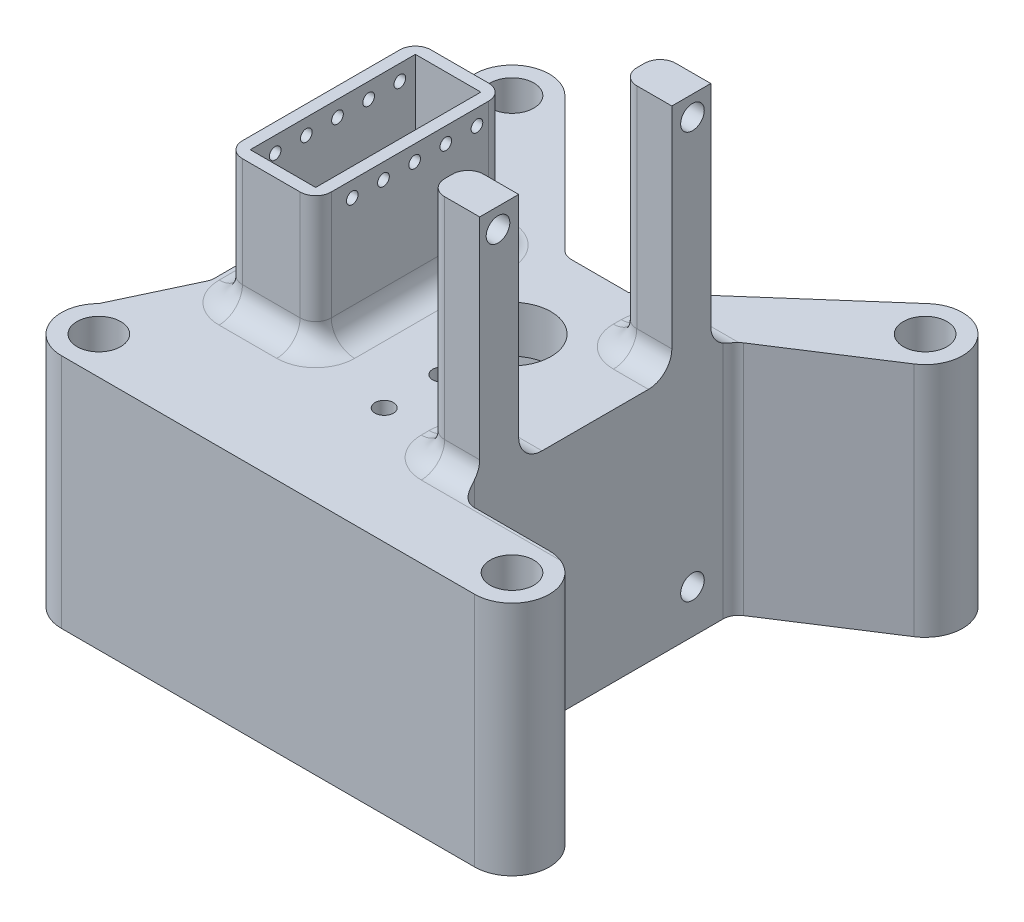
SolidWorks part; units mm, degrees
ref_plane "Front Plane" through (0, 0, 0) normal (0, 0, 1) x (1, 0, 0)
ref_plane "Top Plane" through (0, 0, 0) normal (0, 1, 0) x (1, 0, 0)
ref_plane "Right Plane" through (0, 0, 0) normal (1, 0, 0) x (0, 0, -1)
sketch "Sketch3" plane through (0, 0, 0) normal (0, 1, 0) x (1, 0, 0)
  line L0 (-33.676, -39.772) -> (33.676, -39.772)
  line L1 (-33.676, -33.676) -> (33.676, -33.676) construction
  line L2 (-33.676, -33.676) -> (-33.676, 33.676) construction
  line L3 (-33.676, 33.676) -> (33.676, 33.676) construction
  line L4 (33.676, -33.676) -> (33.676, 33.676) construction
  line L5 (-33.676, -33.676) -> (33.676, 33.676) construction
  line L6 (-33.676, 33.676) -> (33.676, -33.676) construction
  line L7 (10.033, -30.099) -> (-10.033, -30.099)
  line L8 (10.033, -30.099) -> (10.033, 10.033)
  line L9 (10.033, 10.033) -> (3.556, 10.033)
  line L10 (-10.033, -30.099) -> (-10.033, 10.033)
  line L11 (10.033, -30.099) -> (-10.033, 10.033) construction
  line L12 (10.033, 10.033) -> (-10.033, -30.099) construction
  line L13 (33.676, -27.58) -> (18.923, -27.58)
  line L14 (-3.556, 15.367) -> (3.556, 15.367) construction
  line L15 (-3.556, 15.367) -> (-3.556, 10.033)
  line L16 (0, 10.033) -> (3.556, 10.033) construction
  line L17 (3.556, 15.367) -> (3.556, 10.033)
  line L18 (-3.556, 15.367) -> (3.556, 10.033) construction
  line L19 (-3.556, 10.033) -> (3.556, 15.367) construction
  line L20 (-25.781, 10.033) -> (-15.113, 10.033) construction
  line L21 (-25.781, 10.033) -> (-25.781, -16.891) construction
  line L22 (-25.781, -16.891) -> (-15.113, -16.891) construction
  line L23 (-15.113, 10.033) -> (-15.113, -16.891) construction
  line L24 (-25.781, 10.033) -> (-15.113, -16.891) construction
  line L25 (-25.781, -16.891) -> (-15.113, 10.033) construction
  line L26 (18.923, -27.58) -> (18.923, 16.87)
  line L27 (36.9874, 28.5578) -> (18.923, 16.87)
  line L28 (29.6563, 38.259) -> (3.556, 15.367)
  line L31 (0, 10.033) -> (-3.556, 10.033) construction
  line L32 (-29.3669, 37.9879) -> (-6.731, 15.367)
  line L33 (-6.731, 15.367) -> (-3.556, 15.367)
  line L34 (-3.556, 10.033) -> (-10.033, 10.033)
  line L35 (-3.556, 10.033) -> (0, 10.033) construction
  line L36 (3.556, 10.033) -> (0, 10.033) construction
  line L37 (-32.131, -16.891) -> (-32.131, 10.033)
  line L38 (34.003, -24.1637) -> (18.923, -24.1637) construction
  line L39 (34.003, -24.1637) -> (34.003, 13.4537) construction
  line L40 (34.003, 13.4537) -> (18.923, 13.4537) construction
  line L41 (18.923, -24.1637) -> (18.923, 13.4537) construction
  line L42 (34.003, -24.1637) -> (18.923, 13.4537) construction
  line L43 (34.003, 13.4537) -> (18.923, -24.1637) construction
  line L44 (-32.131, 10.033) -> (-39.4519, 31.7268)
  line L45 (-32.131, -16.891) -> (-37.9865, -29.3654)
  circle A0 centre (-33.676, 33.676) radius 3.556
  circle A1 centre (33.676, 33.676) radius 3.556
  circle A2 centre (33.676, -33.676) radius 3.556
  circle A3 centre (-33.676, -33.676) radius 3.556
  circle A4 centre (0, 0) radius 6.35 construction
  circle A5 centre (0, 0) radius 10.033 construction
  circle A6 centre (0, 0) radius 63.373 construction
  arc A7 (33.676, -39.772) -> (33.676, -27.58) centre (33.676, -33.676) ccw
  arc A8 (-39.772, -33.676) -> (-33.676, -39.772) centre (-33.676, -33.676) ccw
  arc A9 (-29.3669, 37.9879) -> (-39.772, 33.676) centre (-33.676, 33.676) ccw
  arc A10 (36.9874, 28.5578) -> (29.6563, 38.259) centre (33.676, 33.676) ccw
  arc A11 (27.58, 33.676) -> (29.3654, 29.3654) centre (33.676, 33.676) ccw construction
  arc A12 (29.6563, 38.259) -> (27.58, 33.676) centre (33.676, 33.676) ccw construction
  arc A13 (29.3654, 29.3654) -> (33.676, 27.58) centre (33.676, 33.676) ccw construction
  arc A14 (33.676, 27.58) -> (36.9874, 28.5578) centre (33.676, 33.676) ccw construction
  arc A15 (-27.58, 33.676) -> (-29.3669, 37.9879) centre (-33.676, 33.676) ccw construction
  arc A16 (-29.3654, 29.3654) -> (-27.58, 33.676) centre (-33.676, 33.676) ccw construction
  arc A17 (-33.676, 27.58) -> (-29.3654, 29.3654) centre (-33.676, 33.676) ccw construction
  arc A18 (-39.772, 33.676) -> (-39.4519, 31.7268) centre (-33.676, 33.676) ccw
  arc A19 (-37.9865, -29.3654) -> (-39.772, -33.676) centre (-33.676, -33.676) ccw
  arc A20 (-29.3654, -29.3654) -> (-33.676, -27.58) centre (-33.676, -33.676) ccw construction
  arc A21 (-27.58, -33.676) -> (-29.3654, -29.3654) centre (-33.676, -33.676) ccw construction
  arc A22 (-33.676, -39.772) -> (-27.58, -33.676) centre (-33.676, -33.676) ccw construction
  arc A23 (33.676, -27.58) -> (29.3654, -29.3654) centre (33.676, -33.676) ccw construction
  arc A24 (29.3654, -29.3654) -> (27.58, -33.676) centre (33.676, -33.676) ccw construction
  arc A25 (27.58, -33.676) -> (33.676, -39.772) centre (33.676, -33.676) ccw construction
  arc A26 (-39.4519, 31.7268) -> (-33.676, 27.58) centre (-33.676, 33.676) ccw construction
  arc A27 (-33.676, -27.58) -> (-37.9865, -29.3654) centre (-33.676, -33.676) ccw construction
  point P0 (0, 0)
  point P10 (0, -10.033)
  point P25 (0, 12.7)
  point P30 (3.556, 12.7)
  point P32 (-20.447, -3.429)
  point P53 (18.923, -5.355)
  point P55 (26.463, -5.355)
  point P64 (-32.131, -3.429)
  dimension "D2" = 7.112
  dimension "D5" = 12.7
  dimension "D6" = 126.746
  dimension "D1" = 95.25
  dimension "D3" = 40.132
  dimension "D4" = 20.066
  dimension "D7" = 2.54
  dimension "D8" = 5.334
  dimension "D9" = 7.112
  dimension "D10" = 10.668
  dimension "D11" = 26.924
  dimension "D12" = 5.08
  dimension "D13" = 8.89
  dimension "D14" = 171.65
  dimension "D15" = 352.506
  dimension "D16" = 44.45
  dimension "D17" = 37.6174
  dimension "D18" = 3.175
  dimension "D19" = 30.16
  dimension "D21" = 6.35
  dimension "D20" = 67.3519
extrude "Boss-Extrude1" add sketch "Sketch3" along normal blind 21.463
sketch "Sketch4" plane through (0, 21.463, 0) normal (0, 1, 0) x (1, 0, 0)
  line L0 (-3.556, 15.367) -> (3.556, 15.367) construction
  line L1 (-3.556, 10.033) -> (3.556, 10.033) construction
  line L2 (3.556, 15.367) -> (-3.556, 15.367)
  line L3 (-3.556, 10.033) -> (3.556, 10.033)
  line L16 (-10.033, 10.033) -> (-3.556, 10.033)
  line L17 (-3.556, 10.033) -> (-3.556, 15.367)
  line L18 (-3.556, 15.367) -> (-6.731, 15.367)
  line L19 (-6.731, 15.367) -> (-29.3669, 37.9879)
  line L20 (-39.4519, 31.7268) -> (-32.131, 10.033)
  line L21 (-33.676, -39.772) -> (33.676, -39.772)
  line L22 (33.676, -27.58) -> (18.923, -27.58)
  line L23 (18.923, -27.58) -> (18.923, 16.87)
  line L24 (18.923, 16.87) -> (36.9874, 28.5578)
  line L25 (29.6563, 38.259) -> (3.556, 15.367)
  line L27 (3.556, 15.367) -> (3.556, 10.033)
  line L28 (3.556, 10.033) -> (10.033, 10.033)
  line L29 (10.033, 10.033) -> (10.033, -30.099)
  line L30 (10.033, -30.099) -> (-10.033, -30.099)
  line L31 (-10.033, -30.099) -> (-10.033, 10.033)
  line L32 (-10.033, 10.033) -> (-3.556, 10.033)
  line L33 (-3.556, 10.033) -> (-3.556, 15.367) construction
  line L34 (-3.556, 15.367) -> (-6.731, 15.367)
  line L35 (-6.731, 15.367) -> (-29.3669, 37.9879)
  line L37 (-33.676, -39.772) -> (33.676, -39.772)
  line L38 (33.676, -27.58) -> (18.923, -27.58)
  line L39 (18.923, -27.58) -> (18.923, 16.87)
  line L40 (18.923, 16.87) -> (36.9874, 28.5578)
  line L41 (29.6563, 38.259) -> (3.556, 15.367)
  line L43 (3.556, 15.367) -> (3.556, 10.033) construction
  line L44 (3.556, 10.033) -> (10.033, 10.033)
  line L45 (10.033, 10.033) -> (10.033, -30.099)
  line L46 (10.033, -30.099) -> (-10.033, -30.099)
  line L47 (-10.033, -30.099) -> (-10.033, 10.033)
  line L52 (-39.4519, 31.7268) -> (-32.131, 10.033)
  line L53 (-32.131, 10.033) -> (-32.131, -16.891)
  line L54 (-32.131, 10.033) -> (-32.131, -16.891)
  line L55 (-32.131, -16.891) -> (-37.9865, -29.3654)
  line L56 (-32.131, -16.891) -> (-37.9865, -29.3654)
  circle A3 centre (33.676, -33.676) radius 3.556 construction
  arc A4 (-29.3669, 37.9879) -> (-39.4519, 31.7268) centre (-33.676, 33.676) ccw
  arc A5 (-37.9865, -29.3654) -> (-33.676, -39.772) centre (-33.676, -33.676) ccw
  arc A6 (33.676, -39.772) -> (33.676, -27.58) centre (33.676, -33.676) ccw
  arc A7 (36.9874, 28.5578) -> (29.6563, 38.259) centre (33.676, 33.676) ccw
  arc A8 (-29.3669, 37.9879) -> (-39.4519, 31.7268) centre (-33.676, 33.676) ccw
  arc A9 (-37.9865, -29.3654) -> (-33.676, -39.772) centre (-33.676, -33.676) ccw
  arc A10 (33.676, -39.772) -> (33.676, -27.58) centre (33.676, -33.676) ccw
  arc A11 (36.9874, 28.5578) -> (29.6563, 38.259) centre (33.676, 33.676) ccw
  circle A12 centre (33.676, -33.676) radius 3.556
  circle A13 centre (33.676, 33.676) radius 3.556 construction
  circle A14 centre (33.676, 33.676) radius 3.556
  circle A15 centre (-33.676, 33.676) radius 3.556 construction
  circle A16 centre (-33.676, 33.676) radius 3.556
  circle A17 centre (-33.676, -33.676) radius 3.556 construction
  circle A18 centre (-33.676, -33.676) radius 3.556
  dimension "D1" = 0
extrude "Boss-Extrude2" add sketch "Sketch4" along normal blind 7.366
sketch "Sketch5" plane through (0, 28.829, 0) normal (0, 1, 0) x (1, 0, 0)
  line L8 (3.556, 15.367) -> (-6.731, 15.367)
  line L9 (-6.731, 15.367) -> (-29.3669, 37.9879)
  line L10 (-39.4519, 31.7268) -> (-32.131, 10.033)
  line L11 (-33.676, -39.772) -> (33.676, -39.772)
  line L12 (33.676, -27.58) -> (18.923, -27.58)
  line L13 (18.923, -27.58) -> (18.923, 16.87)
  line L14 (18.923, 16.87) -> (36.9874, 28.5578)
  line L15 (29.6563, 38.259) -> (3.556, 15.367)
  line L16 (3.556, 15.367) -> (-6.731, 15.367)
  line L17 (-6.731, 15.367) -> (-29.3669, 37.9879)
  line L19 (-33.676, -39.772) -> (33.676, -39.772)
  line L20 (33.676, -27.58) -> (18.923, -27.58)
  line L21 (18.923, -27.58) -> (18.923, 16.87)
  line L22 (18.923, 16.87) -> (36.9874, 28.5578)
  line L23 (29.6563, 38.259) -> (3.556, 15.367)
  line L26 (-39.4519, 31.7268) -> (-32.131, 10.033)
  line L27 (-32.131, 10.033) -> (-32.131, -16.891)
  line L28 (-32.131, 10.033) -> (-32.131, -16.891)
  line L29 (-32.131, -16.891) -> (-37.9865, -29.3654)
  line L30 (-32.131, -16.891) -> (-37.9865, -29.3654)
  circle A0 centre (0, 0) radius 6.35 construction
  circle A1 centre (33.676, 33.676) radius 3.556
  circle A2 centre (33.676, 33.676) radius 3.556
  circle A3 centre (-33.676, 33.676) radius 3.556
  circle A4 centre (-33.676, 33.676) radius 3.556
  circle A5 centre (-33.676, -33.676) radius 3.556
  circle A6 centre (-33.676, -33.676) radius 3.556
  circle A7 centre (33.676, -33.676) radius 3.556
  circle A8 centre (33.676, -33.676) radius 3.556
  circle A9 centre (0, 0) radius 6.35
  arc A12 (-29.3669, 37.9879) -> (-39.4519, 31.7268) centre (-33.676, 33.676) ccw
  arc A13 (-37.9865, -29.3654) -> (-33.676, -39.772) centre (-33.676, -33.676) ccw
  arc A14 (33.676, -39.772) -> (33.676, -27.58) centre (33.676, -33.676) ccw
  arc A15 (36.9874, 28.5578) -> (29.6563, 38.259) centre (33.676, 33.676) ccw
  arc A16 (-29.3669, 37.9879) -> (-39.4519, 31.7268) centre (-33.676, 33.676) ccw
  arc A17 (-37.9865, -29.3654) -> (-33.676, -39.772) centre (-33.676, -33.676) ccw
  arc A18 (33.676, -39.772) -> (33.676, -27.58) centre (33.676, -33.676) ccw
  arc A19 (36.9874, 28.5578) -> (29.6563, 38.259) centre (33.676, 33.676) ccw
  dimension "D1" = 0
  dimension "D2" = 0
  dimension "D3" = 0
  dimension "D4" = 0
  dimension "D5" = 0
extrude "Boss-Extrude3" add sketch "Sketch5" along normal blind 7.62
sketch "Sketch6" plane through (0, 36.449, 0) normal (0, 1, 0) x (1, 0, 0)
  line L0 (-25.781, 10.033) -> (-25.781, -16.891) construction
  line L1 (-25.781, -16.891) -> (-15.113, -16.891) construction
  line L2 (-15.113, 10.033) -> (-15.113, -16.891) construction
  line L3 (-25.781, 10.033) -> (-15.113, 10.033) construction
  line L4 (-25.781, 10.033) -> (-25.781, -16.891) construction
  line L5 (-25.781, -16.891) -> (-15.113, -16.891) construction
  line L6 (-15.113, 10.033) -> (-15.113, -16.891) construction
  line L7 (-25.781, 10.033) -> (-15.113, 10.033) construction
  line L9 (-13.208, 11.938) -> (-27.686, 11.938)
  line L10 (-13.208, 11.938) -> (-13.208, -18.796)
  line L11 (-13.208, -18.796) -> (-27.686, -18.796)
  line L12 (-27.686, 11.938) -> (-27.686, -18.796)
  line L13 (-13.208, 11.938) -> (-27.686, -18.796) construction
  line L14 (-13.208, -18.796) -> (-27.686, 11.938) construction
  point P4 (-20.447, -3.429)
  point P11 (-20.447, -16.891)
  dimension "D1" = 1.905
  dimension "D2" = 1.905
extrude "Boss-Extrude4" add sketch "Sketch6" along normal blind 21.59
sketch "Sketch7" plane through (0, 58.039, 0) normal (0, 1, 0) x (1, 0, 0)
  line L0 (-25.781, 10.033) -> (-25.781, -16.891) construction
  line L1 (-25.781, -16.891) -> (-15.113, -16.891) construction
  line L2 (-15.113, 10.033) -> (-15.113, -16.891) construction
  line L3 (-25.781, 10.033) -> (-15.113, 10.033) construction
  line L4 (-25.781, 10.033) -> (-25.781, -16.891)
  line L5 (-25.781, -16.891) -> (-15.113, -16.891)
  line L6 (-15.113, 10.033) -> (-15.113, -16.891)
  line L7 (-25.781, 10.033) -> (-15.113, 10.033)
extrude "Cut-Extrude1" cut sketch "Sketch7" against normal blind 50.8
sketch "Sketch8" plane through (-27.686, 0, 0) normal (-1, 0, 0) x (0, 0, 1)
  line L0 (16.891, 7.239) -> (16.891, 58.039) construction
  line L1 (-10.033, 7.239) -> (-10.033, 58.039) construction
  line L2 (16.891, 7.239) -> (16.891, 58.039) construction
  line L3 (-10.033, 7.239) -> (-10.033, 58.039) construction
  line L4 (-7.493, 55.499) -> (-2.413, 55.499) construction
  circle A0 centre (-7.493, 55.499) radius 0.9525
  circle A1 centre (-2.413, 55.499) radius 0.9525
  circle A2 centre (2.667, 55.499) radius 0.9525
  circle A3 centre (7.747, 55.499) radius 0.9525
  circle A4 centre (12.827, 55.499) radius 0.9525
  dimension "D1" = 1.905
  dimension "D5" = 5.08
  dimension "D2" = 2.54
  dimension "D3" = 2.54
  dimension "D4" = 5
extrude "Cut-Extrude2" cut sketch "Sketch8" against normal through all
sketch "Sketch10" plane through (0, 36.449, 0) normal (0, 1, 0) x (1, 0, 0)
  line L0 (18.923, -27.58) -> (18.923, 16.87) construction
  line L1 (10.668, -24.19) -> (18.923, -24.19)
  line L2 (10.668, -24.19) -> (10.668, -17.84)
  line L3 (10.668, 13.48) -> (18.923, 13.48)
  line L4 (18.923, -24.19) -> (18.923, -17.84)
  line L5 (10.668, -24.19) -> (18.923, 13.48) construction
  line L6 (10.668, 13.48) -> (18.923, -24.19) construction
  line L7 (18.923, -27.58) -> (18.923, 16.87) construction
  line L8 (18.923, -17.84) -> (18.923, 7.13) construction
  line L9 (18.923, -17.84) -> (10.668, -17.84)
  line L10 (18.923, -17.84) -> (18.923, 7.13) construction
  line L11 (18.923, 7.13) -> (10.668, 7.13)
  line L12 (10.668, -17.84) -> (10.668, 7.13) construction
  line L13 (18.923, -17.84) -> (10.668, 7.13) construction
  line L14 (18.923, 7.13) -> (10.668, -17.84) construction
  line L15 (18.923, 7.13) -> (18.923, 13.48)
  line L16 (10.668, -17.84) -> (10.668, 7.13) construction
  line L17 (10.668, 7.13) -> (10.668, 13.48)
  point P0 (14.7955, -5.355)
  point P7 (18.923, -5.355)
  point P9 (14.7955, -5.355)
  dimension "D1" = 37.67
  dimension "D2" = 8.255
  dimension "D3" = 6.35
extrude "Boss-Extrude5" add sketch "Sketch10" along normal blind 38.1
sketch "Sketch9" plane through (18.923, 0, 0) normal (1, 0, 0) x (0, 0, -1)
  line L0 (-27.58, 0) -> (16.87, 0) construction
  line L1 (-21.205, 71.3) -> (10.495, 71.3) construction
  line L2 (-21.205, 71.3) -> (-21.205, 5) construction
  line L3 (-21.205, 5) -> (10.495, 5) construction
  line L4 (10.495, 71.3) -> (10.495, 5) construction
  line L5 (-21.205, 71.3) -> (10.495, 5) construction
  line L6 (-21.205, 5) -> (10.495, 71.3) construction
  circle A0 centre (-21.205, 71.3) radius 1.925
  circle A1 centre (10.495, 71.3) radius 1.925
  circle A2 centre (10.495, 5) radius 1.925
  circle A3 centre (-21.205, 5) radius 1.925
  point P0 (-5.355, 38.15)
  dimension "D4" = 3.85
  dimension "D1" = 31.7
  dimension "D2" = 66.3
  dimension "D3" = 5
extrude "Cut-Extrude3" cut sketch "Sketch9" against normal blind 5.75
sketch "Sketch13" plane through (0, 36.449, 0) normal (0, 1, 0) x (1, 0, 0)
  line L0 (0, -11.43) -> (0, -20.828) construction
  circle A0 centre (0, -11.43) radius 1.5
  circle A1 centre (0, -20.828) radius 1.5
  dimension "D2" = 3
  dimension "D1" = 9.398
  dimension "D3" = 11.43
extrude "Cut-Extrude4" cut sketch "Sketch13" against normal blind 4
fillet "Fillet1" radius 2.54 13 edges at (10.668, 55.499, 17.84) (10.668, 55.499, 24.19) (10.668, 55.499, -7.13) (10.668, 55.499, -13.48) (-27.686, 47.244, -11.938) (-13.208, 47.244, -11.938) (-13.208, 47.244, 18.796) (-27.686, 47.244, 18.796) (-32.131, 18.2245, 16.891) (-32.131, 18.2245, -10.033) (-6.731, 18.2245, -15.367) (18.923, 18.2245, -16.87) (18.923, 18.2245, 27.58)
fillet "Fillet2" radius 3.81 18 edges at (-13.9519, 36.449, -11.1941) (-13.208, 36.449, 3.429) (-13.9519, 36.449, 18.0521) (-20.447, 36.449, 18.796) (-26.9421, 36.449, 18.0521) (-27.686, 36.449, 3.429) (-26.9421, 36.449, -11.1941) (16.0655, 36.449, 24.19) (11.4119, 36.449, 23.446) (10.668, 36.449, 21.015) (11.4119, 36.449, 18.5839) (16.0655, 36.449, -7.13) (11.4119, 36.449, -7.874) (10.668, 36.449, -10.305) (11.4119, 36.449, -12.7361) (-20.447, 36.449, -11.938) (16.0655, 36.449, 17.84) (16.0655, 36.449, -13.48)
sketch "Sketch14" plane through (0, 0, 0) normal (0, -1, 0) x (1, 0, 0)
  line L17 (-3.556, -10.033) -> (-10.033, -10.033)
  line L18 (-10.033, -10.033) -> (-10.033, 30.099)
  line L19 (-10.033, 30.099) -> (10.033, 30.099)
  line L20 (10.033, 30.099) -> (10.033, -10.033)
  line L21 (10.033, -10.033) -> (3.556, -10.033)
  line L22 (3.556, -10.033) -> (3.556, -15.367)
  line L23 (3.556, -15.367) -> (29.6563, -38.259)
  line L24 (36.9874, -28.5578) -> (20.0832, -17.6207)
  line L25 (18.923, -15.4881) -> (18.923, 25.04)
  line L26 (21.463, 27.58) -> (33.676, 27.58)
  line L27 (33.676, 39.772) -> (-33.676, 39.772)
  line L28 (-37.9865, 29.3654) -> (-32.3717, 17.4038)
  line L29 (-32.131, 16.3245) -> (-32.131, -9.616)
  line L30 (-32.2643, -10.4281) -> (-39.4519, -31.7268)
  line L31 (-29.3669, -37.9879) -> (-7.4748, -16.1104)
  line L32 (-5.6794, -15.367) -> (-3.556, -15.367)
  line L33 (-3.556, -15.367) -> (-3.556, -10.033)
  line L34 (-3.556, -10.033) -> (-10.033, -10.033)
  line L35 (-10.033, -10.033) -> (-10.033, 30.099)
  line L36 (-10.033, 30.099) -> (10.033, 30.099)
  line L37 (10.033, 30.099) -> (10.033, -10.033)
  line L38 (10.033, -10.033) -> (3.556, -10.033)
  line L39 (3.556, -10.033) -> (3.556, -15.367)
  line L40 (3.556, -15.367) -> (29.6563, -38.259)
  line L41 (36.9874, -28.5578) -> (20.0832, -17.6207)
  line L42 (18.923, -15.4881) -> (18.923, 25.04)
  line L43 (21.463, 27.58) -> (33.676, 27.58)
  line L44 (33.676, 39.772) -> (-33.676, 39.772)
  line L45 (-37.9865, 29.3654) -> (-32.3717, 17.4038)
  line L46 (-32.131, 16.3245) -> (-32.131, -9.616)
  line L47 (-32.2643, -10.4281) -> (-39.4519, -31.7268)
  line L48 (-29.3669, -37.9879) -> (-7.4748, -16.1104)
  line L49 (-5.6794, -15.367) -> (-3.556, -15.367)
  line L50 (-3.556, -15.367) -> (-3.556, -10.033)
  circle A0 centre (-33.676, -33.676) radius 3.556 construction
  circle A1 centre (-33.676, -33.676) radius 3.556
  circle A2 centre (-33.676, 33.676) radius 3.556 construction
  circle A3 centre (-33.676, 33.676) radius 3.556
  circle A4 centre (33.676, 33.676) radius 3.556 construction
  circle A5 centre (33.676, 33.676) radius 3.556
  circle A6 centre (33.676, -33.676) radius 3.556 construction
  circle A7 centre (33.676, -33.676) radius 3.556
  arc A9 (29.6563, -38.259) -> (36.9874, -28.5578) centre (33.676, -33.676) ccw
  arc A10 (18.923, -15.4881) -> (20.0832, -17.6207) centre (21.463, -15.4881) ccw
  arc A11 (21.463, 27.58) -> (18.923, 25.04) centre (21.463, 25.04) ccw
  arc A12 (33.676, 27.58) -> (33.676, 39.772) centre (33.676, 33.676) ccw
  arc A13 (-33.676, 39.772) -> (-37.9865, 29.3654) centre (-33.676, 33.676) ccw
  arc A14 (-32.131, 16.3245) -> (-32.3717, 17.4038) centre (-34.671, 16.3245) ccw
  arc A15 (-32.2643, -10.4281) -> (-32.131, -9.616) centre (-34.671, -9.616) ccw
  arc A16 (-39.4519, -31.7268) -> (-29.3669, -37.9879) centre (-33.676, -33.676) ccw
  arc A17 (-5.6794, -15.367) -> (-7.4748, -16.1104) centre (-5.6794, -17.907) ccw
  arc A18 (29.6563, -38.259) -> (36.9874, -28.5578) centre (33.676, -33.676) ccw
  arc A19 (18.923, -15.4881) -> (20.0832, -17.6207) centre (21.463, -15.4881) ccw
  arc A20 (21.463, 27.58) -> (18.923, 25.04) centre (21.463, 25.04) ccw
  arc A21 (33.676, 27.58) -> (33.676, 39.772) centre (33.676, 33.676) ccw
  arc A22 (-33.676, 39.772) -> (-37.9865, 29.3654) centre (-33.676, 33.676) ccw
  arc A23 (-32.131, 16.3245) -> (-32.3717, 17.4038) centre (-34.671, 16.3245) ccw
  arc A24 (-32.2643, -10.4281) -> (-32.131, -9.616) centre (-34.671, -9.616) ccw
  arc A25 (-39.4519, -31.7268) -> (-29.3669, -37.9879) centre (-33.676, -33.676) ccw
  arc A26 (-5.6794, -15.367) -> (-7.4748, -16.1104) centre (-5.6794, -17.907) ccw
  dimension "D1" = 0
extrude "Boss-Extrude6" add sketch "Sketch14" along normal blind 2.0585
equation "\"AIRFRAME_OD\"= 5.15in"
equation "\"AIRFRAME_ID\"= 4.99in"
equation "\"FLAT_T\"= 0.125in"
equation "\"COUPLER_OD\"= 4.998in"
equation "\"COUPLER_ID\"= 4.85in"
equation "\"NOSE_EXP_L\"= 27in"
equation "\"NOSE_SHOULDER_L\"= 5in"
equation "\"MAIN_L\"= 30in"
equation "\"RECO_COUP_L\"= 10in"
equation "\"RECO_SWITCH_L\"= 2in"
equation "\"RECO_ROD_X\"= 3.5in"
equation "\"DROGUE_L\"= 20in"
equation "\"ATS_FORE_COUP_L\"= 5.5in"
equation "\"ATS_AFT_COUP_L\"= 4.5in"
equation "\"ATS_ROD_X\"= 3.75in"
equation "\"LOWER_L\"= 30in"
equation "\"FIN_ROOT\"= 8in"
equation "\"FIN_X\"= 0.75in"
equation "\"FIN_N\"= 4"
equation "\"MOTOR_OD\"= 3.091in"
equation "\"MOTOR_ID\"= 3.00in"
equation "\"MOTOR_L\"= 14in"
equation "\"CR_AFT_X\"= 0.5in"
equation "\"CR_FORE_X\"= 9.25in"
equation "\"MOTOR_LOWER_X\"= 2in"
equation "\"D1@Sketch3\"=\"ATS_ROD_X\""
equation "\"D6@Sketch3\"=\"AIRFRAME_ID\""
